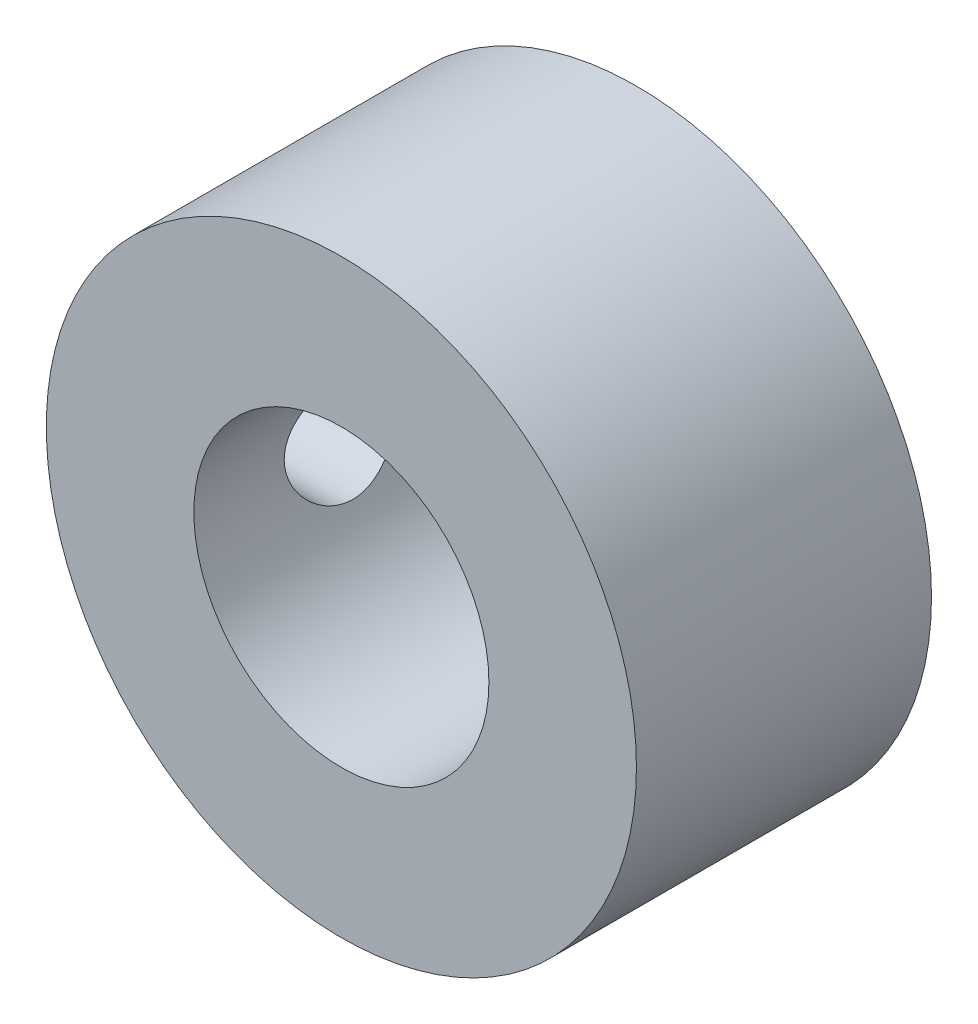
SolidWorks part; units mm, degrees
ref_plane "Front Plane" through (0, 0, 0) normal (0, 0, 1) x (1, 0, 0)
ref_plane "Top Plane" through (0, 0, 0) normal (0, 1, 0) x (1, 0, 0)
ref_plane "Right Plane" through (0, 0, 0) normal (1, 0, 0) x (0, 0, -1)
sketch "Sketch1" plane through (0, 0, 0) normal (0, 0, 1) x (1, 0, 0)
  circle A0 centre (0, 0) radius 4
  circle A1 centre (0, 0) radius 8
extrude "Boss-Extrude1" add sketch "Sketch1" along normal blind 8
ref_axis "Axis1" through (0, 0, 8) along (0, 0, -1)
ref_plane "Plane1" through (0, 0, 0) normal (1, 0, 0) x (0, 0, -1)
sketch "Sketch2" plane through (0, 0, 0) normal (1, 0, 0) x (0, 0, -1)
  line L0 (-8, 0) -> (0, 0) construction
  line L1 (-8, 8) -> (-8, -8) construction
  circle A0 centre (-4, 0) radius 1.55
extrude "Cut-Extrude1" cut sketch "Sketch2" against normal up to surface (8 mm away) up to face at (8, 0, 8)
